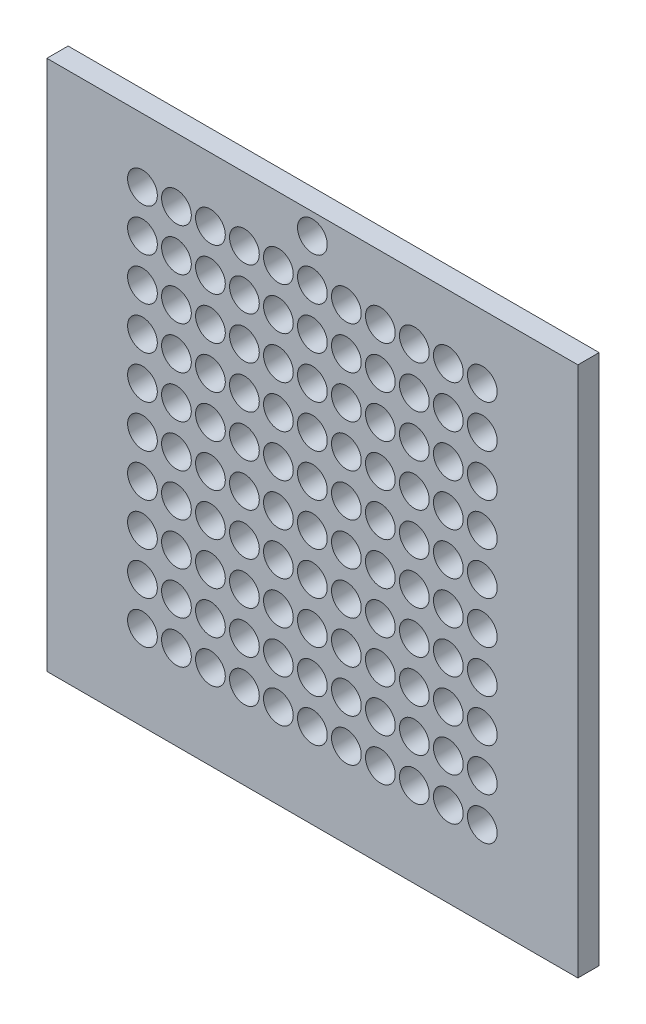
SolidWorks part; units mm, degrees
ref_plane "Ebene vorne" through (0, 0, 0) normal (0, 0, 1) x (1, 0, 0)
ref_plane "Ebene oben" through (0, 0, 0) normal (0, 1, 0) x (1, 0, 0)
ref_plane "Ebene rechts" through (0, 0, 0) normal (1, 0, 0) x (0, 0, -1)
sketch "Skizze2" plane through (0, 0, 0) normal (0, 0, 1) x (1, 0, 0)
  line L0 (-62.5, 62.5) -> (-62.5, -62.5) construction
  line L1 (-62.5, -62.5) -> (62.5, -62.5) construction
  line L2 (62.5, 62.5) -> (-62.5, 62.5) construction
  line L3 (62.5, -62.5) -> (62.5, 62.5) construction
  line L4 (-62.5, 62.5) -> (-62.5, -62.5)
  line L5 (-62.5, -62.5) -> (62.5, -62.5)
  line L6 (62.5, 62.5) -> (-62.5, 62.5)
  line L7 (62.5, -62.5) -> (62.5, 62.5)
extrude "Aufsatz-Linear austragen1" add sketch "Skizze2" along normal blind 5
sketch "Skizze3" plane through (0, 0, 0) normal (0, 0, -1) x (-1, 0, 0)
  line L0 (0, 62.5) -> (0, 0) construction
  line L1 (-62.5, 62.5) -> (62.5, 62.5) construction
  line L2 (-67.5, 67.5) -> (67.5, 67.5) construction
  circle A0 centre (0, 57.5) radius 3.5
  dimension "D1" = 7
  dimension "D2" = 10
extrude "Schnitt-Linear austragen1" cut sketch "Skizze3" against normal up to surface (5 mm away) up to face at (0, 0, 5)
sketch "Skizze4" plane through (0, 0, 0) normal (0, 0, -1) x (-1, 0, 0)
  line L0 (0, 0) -> (0, 62.5) construction
  line L1 (-62.5, 62.5) -> (62.5, 62.5) construction
  line L2 (-67.5, 67.5) -> (67.5, 67.5) construction
  circle A0 centre (0, 47.5) radius 3.5
  dimension "D1" = 7
  dimension "D2" = 20
extrude "Schnitt-Linear austragen2" cut sketch "Skizze4" against normal up to surface (5 mm away) up to face at (3.5, 57.5, 5)
pattern_linear "Lineares Muster1" count 6 spacing 8 along (1, 0, 0) count 10 spacing 10 along (0, -1, 0) of "Schnitt-Linear austragen2"
pattern_linear "Lineares Muster2" count 6 spacing 8 along (-1, 0, 0) count 10 spacing 10 along (0, -1, 0) skipping (0, 1), (0, 2), (0, 3), (0, 4), (0, 5), (0, 6), (0, 7), (0, 8), (0, 9) of "Schnitt-Linear austragen2"
sketch "Skizze5" plane through (0, 0, 0) normal (0, 0, -1) x (-1, 0, 0)
  line L0 (-67.5, -67.5) -> (-67.5, 67.5) construction
  line L1 (-67.5, 67.5) -> (67.5, 67.5) construction
  line L2 (67.5, 67.5) -> (67.5, -67.5) construction
  line L3 (67.5, -67.5) -> (-67.5, -67.5) construction
  circle A0 centre (-50, 50) radius 5.5
  circle A1 centre (50, 50) radius 5.5
  circle A2 centre (-50, -50) radius 5.5
  circle A3 centre (50, -50) radius 5.5
  dimension "D1" = 11
  dimension "D3" = 17.5
  dimension "D4" = 11
  dimension "D5" = 17.5
  dimension "D6" = 17.5
  dimension "D7" = 11
  dimension "D8" = 11
  dimension "D9" = 17.5
  dimension "D10" = 17.5
  dimension "D11" = 17.5
  dimension "D12" = 17.5
  dimension "D2" = 17.5
extrude "Schnitt-Linear austragen3" cut sketch "Skizze5" against normal blind 1
